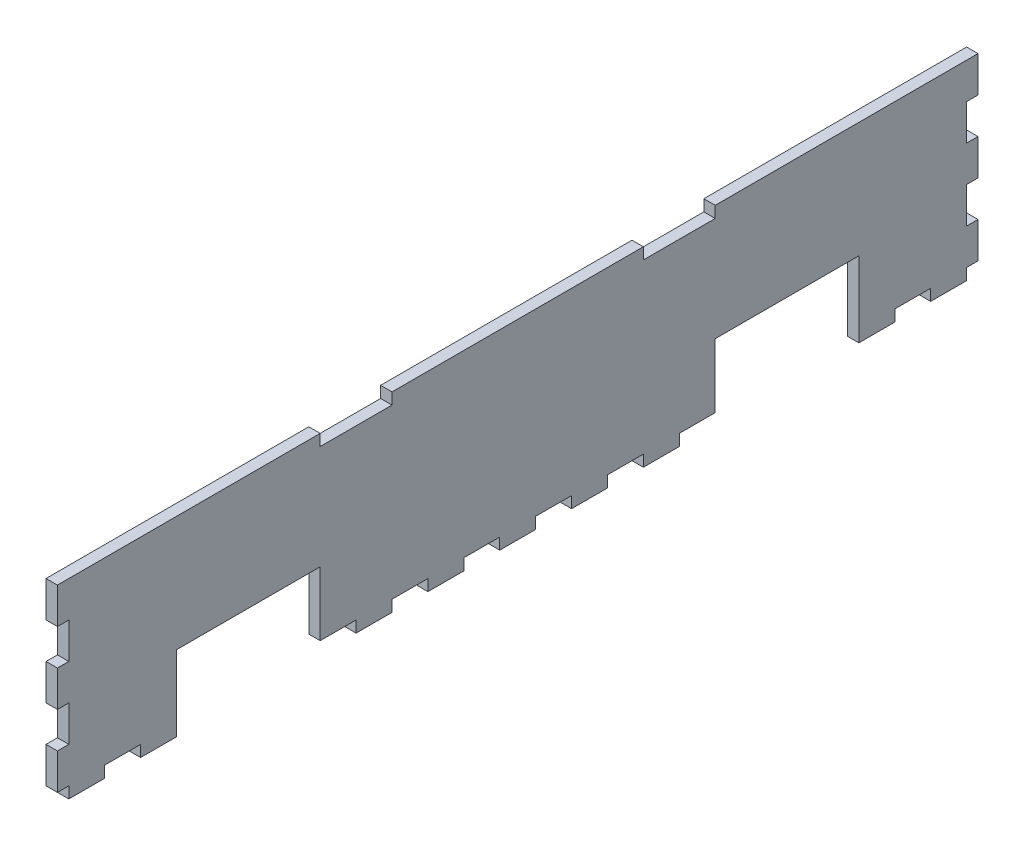
SolidWorks part; units mm, degrees
ref_plane "Plan de face" through (0, 0, 0) normal (0, 0, 1) x (1, 0, 0)
ref_plane "Plan de dessus" through (0, 0, 0) normal (0, 1, 0) x (1, 0, 0)
ref_plane "Plan de droite" through (0, 0, 0) normal (1, 0, 0) x (0, 0, -1)
sketch "Esquisse1" plane through (0, 0, 0) normal (1, 0, 0) x (0, 0, -1)
  line L1 (0, 0) -> (250, 0)
  line L2 (0, 0) -> (0, 50)
  line L3 (0, 50) -> (250, 50)
  line L4 (250, 0) -> (250, 50)
  dimension "D1" = 250
  dimension "D2" = 50
extrude "Boss.-Extru.1" add sketch "Esquisse1" along normal blind 3.175
sketch "Esquisse2" plane through (3.175, 0, 0) normal (1, 0, 0) x (0, 0, -1)
  line L1 (0, 0) -> (10, 0)
  line L2 (0, 0) -> (0, -3.175)
  line L3 (0, -3.175) -> (10, -3.175)
  line L4 (10, 0) -> (10, -3.175)
  dimension "D1" = 10
  dimension "D2" = 3.175
extrude "Boss.-Extru.2" add sketch "Esquisse2" against normal blind 3.175
pattern_linear "Répétition linéaire1" count 13 spacing 20 along (0, 0, -1) of "Boss.-Extru.2"
sketch "Esquisse4" plane through (3.175, 0, 0) normal (1, 0, 0) x (0, 0, -1)
  line L0 (250, 50) -> (0, 50) construction
  line L1 (30, -3.175) -> (70, -3.175)
  line L2 (30, -3.175) -> (30, 17.825)
  line L3 (30, 17.825) -> (70, 17.825)
  line L4 (70, -3.175) -> (70, 17.825)
  line L5 (220, -3.175) -> (180, -3.175)
  line L6 (220, -3.175) -> (220, 17.825)
  line L7 (220, 17.825) -> (180, 17.825)
  line L8 (180, -3.175) -> (180, 17.825)
  line L9 (70, 50) -> (90, 50)
  line L10 (70, 50) -> (70, 46.825)
  line L11 (70, 46.825) -> (90, 46.825)
  line L12 (90, 50) -> (90, 46.825)
  line L14 (180, 50) -> (160, 50)
  line L15 (180, 50) -> (180, 46.825)
  line L16 (180, 46.825) -> (160, 46.825)
  line L17 (160, 50) -> (160, 46.825)
  dimension "D1" = 21
  dimension "D2" = 21
  dimension "D3" = 3.175
  dimension "D4" = 3.175
extrude "Enlèv. mat.-Extru.1" cut sketch "Esquisse4" against normal blind 3.175
sketch "Esquisse5" plane through (3.175, 0, 0) normal (1, 0, 0) x (0, 0, -1)
  line L1 (0, 50) -> (-3.175, 50)
  line L2 (0, 50) -> (0, 40)
  line L3 (0, 40) -> (-3.175, 40)
  line L4 (-3.175, 50) -> (-3.175, 40)
  line L5 (250, 50) -> (253.175, 50)
  line L6 (250, 50) -> (250, 40)
  line L7 (250, 40) -> (253.175, 40)
  line L8 (253.175, 50) -> (253.175, 40)
  dimension "D1" = 3.175
  dimension "D2" = 10
  dimension "D3" = 10
  dimension "D4" = 3.175
extrude "Boss.-Extru.3" add sketch "Esquisse5" against normal blind 3.175
pattern_linear "Répétition linéaire2" count 3 spacing 20 along (0, -1, 0) of "Boss.-Extru.3"
